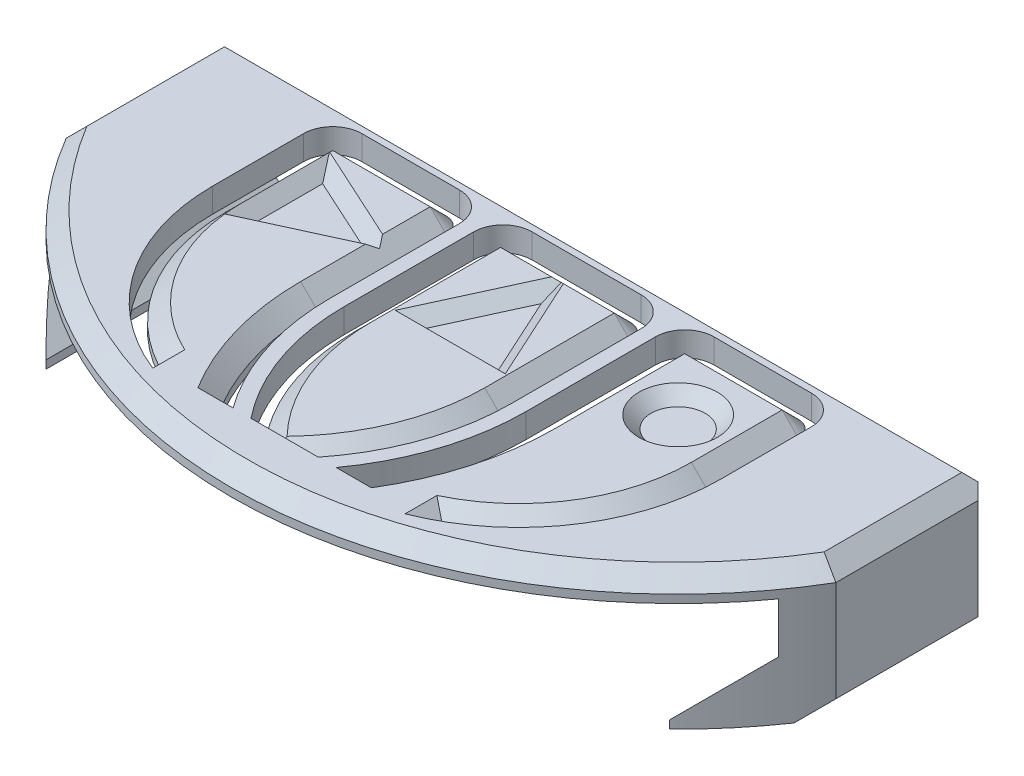
SolidWorks part; units mm, degrees
ref_plane "Front Plane" through (0, 0, 0) normal (0, 0, 1) x (1, 0, 0)
ref_plane "Top Plane" through (0, 0, 0) normal (0, 1, 0) x (1, 0, 0)
ref_plane "Right Plane" through (0, 0, 0) normal (1, 0, 0) x (0, 0, -1)
sketch "Sketch1" plane through (0, 0, 0) normal (0, 1, 0) x (1, 0, 0)
  line L20 (-19.2, 7.5) -> (-19.2, -7.9922)
  line L21 (19.2, 7.5) -> (19.2, -7.9922)
  line L29 (-4.5, -3.6738) -> (-4.5, 4.3)
  line L30 (-3.5, 5.3) -> (3.5, 5.3)
  line L31 (4.5, -3.6738) -> (4.5, 4.3)
  line L32 (-15.6377, 4.3) -> (-15.6377, -1.291)
  line L33 (-13.8377, 6.1) -> (-7.8377, 6.1) construction
  line L35 (6.8377, -3.6738) -> (6.8377, 4.3)
  line L36 (7.8377, 5.3) -> (13.8377, 5.3)
  line L37 (14.8377, -1.291) -> (14.8377, 4.3)
  line L41 (-14.8377, -1.291) -> (-14.8377, 4.3)
  line L42 (-13.8377, 5.3) -> (-7.8377, 5.3)
  line L43 (-6.8377, -3.6738) -> (-6.8377, 4.3)
  line L46 (-2.8, -11.5) -> (-2, -11.5)
  line L47 (-5.1594, -3.6738) -> (-5.1594, 4.3)
  line L48 (-3.3594, 6.1) -> (3.3594, 6.1) construction
  line L49 (5.1594, -3.6738) -> (5.1594, 4.3)
  line L50 (2.8, -11.5) -> (2, -11.5)
  line L51 (-6.0377, 4.3) -> (-6.0377, -3.6738)
  line L52 (15.6377, -1.291) -> (15.6377, 4.3)
  line L53 (13.8377, 6.1) -> (7.8377, 6.1) construction
  line L54 (6.0377, 4.3) -> (6.0377, -3.6738)
  line L55 (-8.7689, -11.5) -> (-8.7689, -12.4022)
  line L56 (-4.7689, -11.5) -> (-3.8406, -11.5)
  line L57 (3.8406, -11.5) -> (4.7689, -11.5)
  line L58 (8.7689, -11.5) -> (8.7689, -12.4022)
  line L65 (-23.7, 7.5) -> (23.7, 7.5)
  line L66 (-23.7, 7.5) -> (-23.7, -2.2528)
  line L68 (23.7, 7.5) -> (23.7, -2.2528)
  line L87 (-13.8377, 6.1) -> (-7.8377, 6.1)
  line L88 (-3.3594, 6.1) -> (3.3594, 6.1)
  line L89 (7.8377, 6.1) -> (13.8377, 6.1)
  circle A3 centre (0, 11.6956) radius 25 construction
  circle A4 centre (0, 11.6956) radius 27.5 construction
  arc A5 (-14.8377, -1.291) -> (-8.7689, -11.5) centre (-3.2164, -1.291) ccw
  arc A6 (-6.8377, -3.6738) -> (-4.7689, -11.5) centre (9, -3.6738) ccw
  arc A7 (4.5, -3.6738) -> (2, -11.5) centre (-9, -3.6738) cw
  arc A8 (-4.5, -3.6738) -> (-2, -11.5) centre (9, -3.6738) ccw
  arc A9 (6.8377, -3.6738) -> (4.7689, -11.5) centre (-9, -3.6738) cw
  arc A10 (14.8377, -1.291) -> (8.7689, -11.5) centre (3.2164, -1.291) cw
  arc A11 (4.5, 4.3) -> (3.5, 5.3) centre (3.5, 4.3) ccw
  arc A12 (-3.5, 5.3) -> (-4.5, 4.3) centre (-3.5, 4.3) ccw
  arc A13 (-2.8, -11.5) -> (-5.1594, -3.6738) centre (9, -3.6738) cw
  arc A14 (-3.3594, 6.1) -> (-5.1594, 4.3) centre (-3.3594, 4.3) ccw
  arc A15 (3.3594, 6.1) -> (5.1594, 4.3) centre (3.3594, 4.3) cw
  arc A16 (2.8, -11.5) -> (5.1594, -3.6738) centre (-9, -3.6738) ccw
  arc A17 (-15.6377, -1.291) -> (-8.7689, -12.4022) centre (-3.2164, -1.291) ccw
  arc A18 (-6.0377, -3.6738) -> (-3.8406, -11.5) centre (9, -3.6738) ccw
  arc A19 (6.0377, -3.6738) -> (3.8406, -11.5) centre (-9, -3.6738) cw
  arc A20 (15.6377, -1.291) -> (8.7689, -12.4022) centre (3.2164, -1.291) cw
  arc A21 (-6.8377, 4.3) -> (-7.8377, 5.3) centre (-7.8377, 4.3) ccw
  arc A22 (-13.8377, 5.3) -> (-14.8377, 4.3) centre (-13.8377, 4.3) ccw
  arc A23 (15.6377, 4.3) -> (13.8377, 6.1) centre (13.8377, 4.3) ccw
  arc A24 (7.8377, 6.1) -> (6.0377, 4.3) centre (7.8377, 4.3) ccw
  arc A25 (-6.0377, 4.3) -> (-7.8377, 6.1) centre (-7.8377, 4.3) ccw
  arc A26 (-13.8377, 6.1) -> (-15.6377, 4.3) centre (-13.8377, 4.3) ccw
  arc A27 (14.8377, 4.3) -> (13.8377, 5.3) centre (13.8377, 4.3) ccw
  arc A28 (7.8377, 5.3) -> (6.8377, 4.3) centre (7.8377, 4.3) ccw
  arc A36 (-23.7, -2.2528) -> (23.7, -2.2528) centre (0, 11.6956) ccw
  point P0 (0, 0)
  point P16 (0, -4)
  point P66 (0, 6.1)
  dimension "D11" = 50
  dimension "D18" = 55
  dimension "D20" = 4
  dimension "D21" = 1
  dimension "D24" = 1.8
  dimension "D36" = 1
  dimension "D40" = 1.8
  dimension "D41" = 1
  dimension "D12" = 4.5
  dimension "D13" = 4.5
  dimension "D22" = 0.8
  dimension "D23" = 0.8
  dimension "D25" = 9
  dimension "D26" = 8
  dimension "D31" = 4
  dimension "D32" = 4
  dimension "D33" = 0.8
  dimension "D34" = 0.8
  dimension "D35" = 0.8
  dimension "D37" = 0.8
  dimension "D38" = 0.8
  dimension "D39" = 0.8
  dimension "D42" = 47.4
extrude "Boss-Extrude3" add sketch "Sketch1" along normal blind 1.5 contours L20 A36 L21 L65 L36 A28 L35 A9 L57 A19 L54 A24 L89 A23 L52 A20 L58 A10 L37 A27 A16 L50 A7 L31 A11 L30 A12 L29 A8 L46 A13 L47 A14 L88 A15 L49 A26 L87 A25 L51 A18 L56 A6 L43 A21 L42 A22 L41 | L66 A36 L20 L65 | L21 A36 L68 L65 region at (0, 0, 3.2527) region at (-21.2845, 0, -0.9524) region at (21.2845, 0, -0.9524)
extrude "Boss-Extrude4" add sketch "Sketch1<9>" against normal blind 6.7 contours L66 A36 L20 L65 | L21 A36 L68 L65 region at (-21.2845, 0, -0.9524) region at (21.2845, 0, -0.9524)
sketch "Sketch1<9>" plane through (0, 0, 0) normal (0, 1, 0) x (1, 0, 0) same geometry as "Sketch1"
sketch "Sketch3" plane through (0, 0, -7.5) normal (0, 0, -1) x (-1, 0, 0)
  line L0 (-19.2, -6.2) -> (-22.3, -3.1)
  line L1 (-19.2, -6.7) -> (-19.2, 0) construction
  line L2 (-22.3, -3.1) -> (-22.3, 0)
  line L3 (-22.3, 0) -> (-19.2, 0)
  line L4 (-19.2, 0) -> (-19.2, -6.2)
  line L5 (0, 0) -> (0, 15.5927) construction
  line L6 (19.2, 0) -> (-19.2, 0) construction
  line L7 (-19.2, -6.7) -> (-23.7, -6.7) construction
  line L8 (22.3, 0) -> (19.2, 0)
  line L9 (22.3, -3.1) -> (22.3, 0)
  line L10 (19.2, -6.2) -> (22.3, -3.1)
  line L11 (19.2, 0) -> (19.2, -6.2)
  dimension "D1" = 0.5
  dimension "D2" = 45
  dimension "D3" = 3.1
extrude "Cut-Extrude2" cut sketch "Sketch3" against normal up to next
chamfer "Chamfer1" distance 1 angle 45 3 edges at (23.7, 1.5, -2.6236) (0, 1.5, 15.8044) (-23.7, 1.5, -2.6236)
chamfer "Chamfer2" distance 1 angle 45 27 edges at (8.7689, 1.5, 11.9511) (13.2059, 1.5, 7.2293) (14.8377, 1.5, -1.5045) (14.5448, 1.5, -5.0071) (10.8377, 1.5, -5.3) (7.1305, 1.5, -5.0071) (6.8377, 1.5, -0.3131) (6.3117, 1.5, 7.7213) (4.3047, 1.5, 11.5) (2.4, 1.5, 11.5) (3.8598, 1.5, 7.7817) (4.5, 1.5, -0.3131) (4.2071, 1.5, -5.0071) (0, 1.5, -5.3) (-4.2071, 1.5, -5.0071) (-4.5, 1.5, -0.3131) (-3.8598, 1.5, 7.7817) (-2.4, 1.5, 11.5) (-4.3047, 1.5, 11.5) (-6.3117, 1.5, 7.7213) (-6.8377, 1.5, -0.3131) (-7.1305, 1.5, -5.0071) (-10.8377, 1.5, -5.3) (-14.5448, 1.5, -5.0071) (-14.8377, 1.5, -1.5045) (-8.7689, 1.5, 11.9511) (-13.2059, 1.5, 7.2293)
chamfer "Chamfer3" distance 1 angle 45 5 edges at (23.7, -6.7, -2.6236) (23.7, -3.1, -7.5) (0, 1.5, -7.5) (-23.7, -6.7, -2.6236) (-23.7, -3.1, -7.5)
sketch "Sketch5" plane through (0, 1.5, 0) normal (0, 1, 0) x (1, 0, 0)
  line L0 (-13.1267, 2.9674) -> (-13.1267, -1.285)
  line L1 (-13.1267, -1.285) -> (-8.4841, 0.8412)
  line L2 (-8.4841, 0.8412) -> (-13.1267, 2.9674)
  line L3 (0, 3.2971) -> (-2.2187, -1.5473)
  line L4 (-2.2187, -1.5473) -> (2.2187, -1.5473)
  line L5 (2.2187, -1.5473) -> (0, 3.2971)
  line L6 (0, 0) -> (0, 3.2971) construction
  line L7 (-13.1267, 0.8412) -> (-8.4841, 0.8412) construction
  circle A0 centre (10.8935, 0.8412) radius 2.4141
extrude "Cut-Extrude4" cut sketch "Sketch5" against normal blind 0.75
chamfer "Chamfer4" distance 0.75 angle 45 7 edges at (-1.1093, 1.5, -0.8749) (0, 1.5, 1.5473) (1.1093, 1.5, -0.8749) (10.8935, 0.75, 1.5728) (-10.8054, 1.5, 0.2219) (-10.8054, 1.5, -1.9043) (-13.1267, 1.5, -0.8412)
